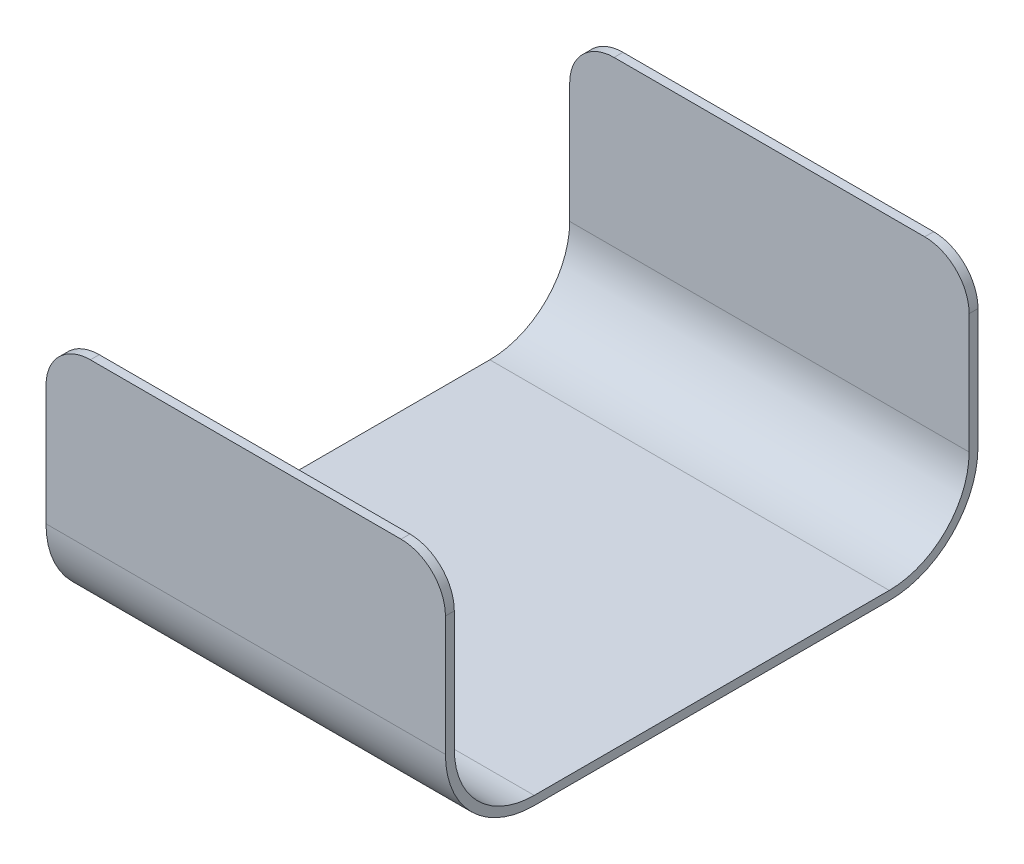
SolidWorks part; units mm, degrees
ref_plane "Front Plane" through (0, 0, 0) normal (0, 0, 1) x (1, 0, 0)
ref_plane "Top Plane" through (0, 0, 0) normal (0, 1, 0) x (1, 0, 0)
ref_plane "Right Plane" through (0, 0, 0) normal (1, 0, 0) x (0, 0, -1)
ref_axis "X" through (88.99, 0, 0) along (-1, 0, 0)
ref_axis "Y" through (0, 55, 0) along (0, -1, 0)
ref_axis "Z" through (0, 0, -88.99) along (0, 0, 1)
sketch "Sketch1" plane through (0, 0, 0) normal (0, 0, 1) x (1, 0, 0)
  line L1 (-45, -28.5) -> (45, -28.5)
  line L2 (-45, -28.5) -> (-45, 28.5)
  line L3 (-45, 28.5) -> (45, 28.5)
  line L4 (45, -28.5) -> (45, 28.5)
  line L5 (-45, -28.5) -> (45, 28.5) construction
  line L6 (-45, 28.5) -> (45, -28.5) construction
  point P0 (0, 0)
  dimension "D1" = 57
  dimension "D2" = 90
extrude "Boss-Extrude1" add sketch "Sketch1" along normal mid plane 120
fillet "Fillet1" radius 20 2 edges at (0, -28.5, -60) (0, -28.5, 60)
shell "Shell1" thickness 2 removed face at (-45, -4.214, 0) removed face at (45, -4.214, 0) removed face at (0, 28.5, 0)
fillet "Fillet2" radius 10 4 edges at (45, 28.5, -59) (-45, 28.5, -59) (45, 28.5, 59) (-45, 28.5, 59)
